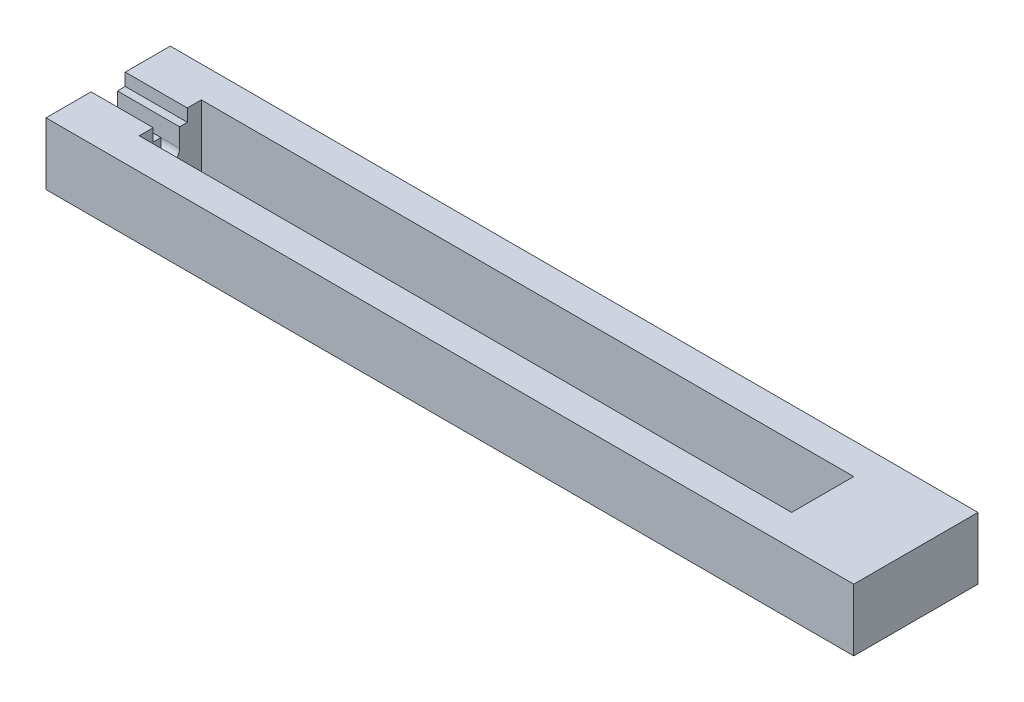
SolidWorks part; units mm, degrees
ref_plane "Front Plane" through (0, 0, 0) normal (0, 0, 1) x (1, 0, 0)
ref_plane "Top Plane" through (0, 0, 0) normal (0, 1, 0) x (1, 0, 0)
ref_plane "Right Plane" through (0, 0, 0) normal (1, 0, 0) x (0, 0, -1)
sketch "Sketch1" plane through (0, 0, 0) normal (0, 1, 0) x (1, 0, 0)
  line L1 (-6.5, -1) -> (6.5, -1)
  line L2 (-6.5, -1) -> (-6.5, 1)
  line L3 (-6.5, 1) -> (6.5, 1)
  line L4 (6.5, -1) -> (6.5, 1)
  line L5 (-6.5, -1) -> (6.5, 1) construction
  line L6 (-6.5, 1) -> (6.5, -1) construction
  line L7 (-5.5, 0.5) -> (5, 0.5)
  line L8 (-5.5, 0.5) -> (-5.5, -0.5)
  line L9 (-5.5, -0.5) -> (5, -0.5)
  line L10 (5, 0.5) -> (5, -0.5)
  point P0 (0, 0)
  point P6 (0, 0)
  dimension "D1" = 2
  dimension "D2" = 13
  dimension "D3" = 1
  dimension "D4" = 1.5
  dimension "D5" = 1
extrude "Boss-Extrude1" add sketch "Sketch1" along normal blind 1
sketch "Sketch2" plane through (-6.5, 0, 0) normal (-1, 0, 0) x (0, 0, 1)
  line L0 (0.15, 0.8) -> (0.275, 0.8)
  line L1 (-1, 1) -> (1, 1) construction
  line L3 (0.15, 0.5) -> (0.15, 0.8)
  line L4 (0.15, 1) -> (-0.15, 1)
  line L5 (1, 1) -> (1, 0) construction
  line L6 (-0.15, 0.5) -> (-0.15, 0.8)
  line L7 (-1, 0) -> (1, 0) construction
  line L9 (-0.275, 0.8) -> (-0.15, 0.8)
  line L10 (-0.275, 0.8) -> (-0.275, 1)
  line L11 (-0.275, 1) -> (0.275, 1)
  line L12 (0.275, 0.8) -> (0.275, 1)
  arc A0 (-0.15, 0.5) -> (0.15, 0.5) centre (0, 0.5) ccw
  point P12 (0, 0.9)
  line M3 (1, 1) -> (-1, 1)
  dimension "D1" = 0.55
  dimension "D2" = 0.2
  dimension "D3" = 1
  dimension "D4" = 0
  dimension "D5" = 0.5
extrude "Cut-Extrude2" cut sketch "Sketch2" against normal blind 1 contours L6 A0 L3 L0 L12 L10 L9 M3 region at (-6.5, 0.7348, 0)
ref_plane "Plane1" through (0, 0.5, 0) normal (0, -1, 0) x (-1, 0, 0)
